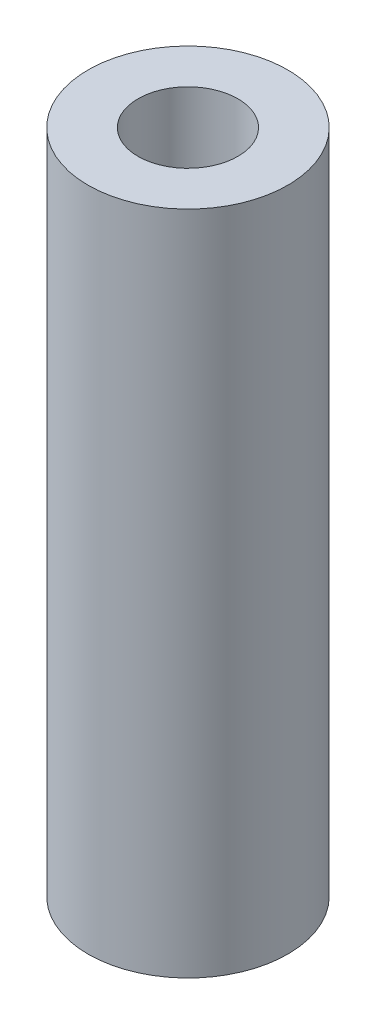
SolidWorks part; units mm, degrees
ref_plane "Front Plane" through (0, 0, 0) normal (0, 0, 1) x (1, 0, 0)
ref_plane "Top Plane" through (0, 0, 0) normal (0, 1, 0) x (1, 0, 0)
ref_plane "Right Plane" through (0, 0, 0) normal (1, 0, 0) x (0, 0, -1)
sketch "Sketch1" plane through (0, 0, 0) normal (0, 1, 0) x (1, 0, 0)
  circle A0 centre (0, 0) radius 1.5
  circle A1 centre (0, 0) radius 3
  dimension "D1" = 3
  dimension "D2" = 6
extrude "Boss-Extrude1" add sketch "Sketch1" along normal blind 20 contours A1 | A0
